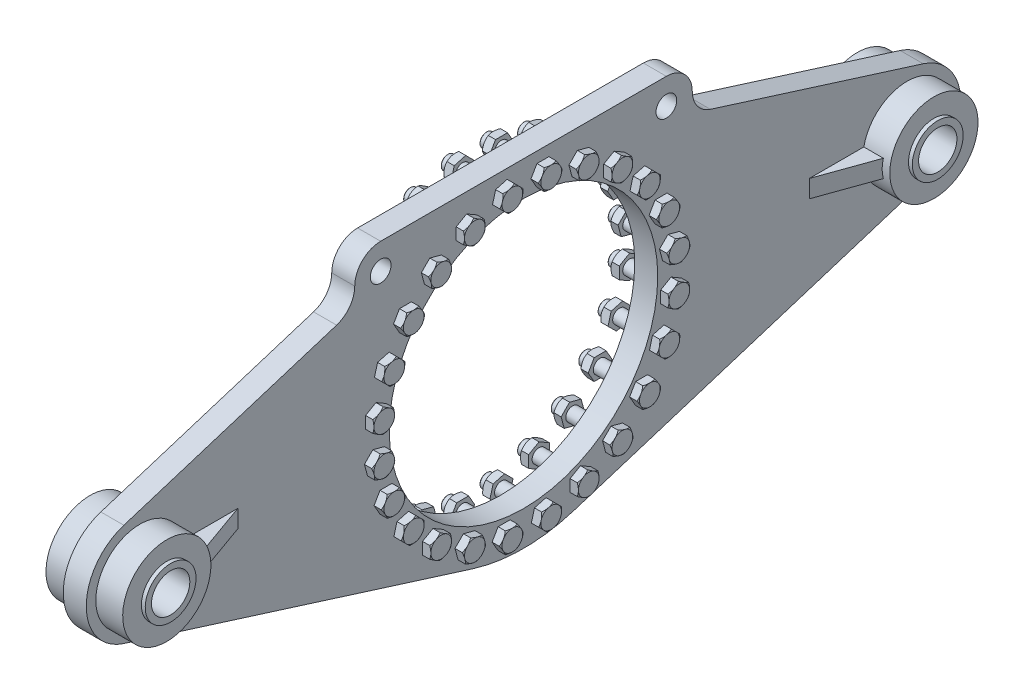
SolidWorks part; units mm, degrees
ref_plane "前视基准面" through (0, 0, 0) normal (0, 0, 1) x (1, 0, 0)
ref_plane "上视基准面" through (0, 0, 0) normal (0, 1, 0) x (1, 0, 0)
ref_plane "右视基准面" through (0, 0, 0) normal (1, 0, 0) x (0, 0, -1)
sketch "草图1" plane through (0, 0, 0) normal (1, 0, 0) x (0, 0, -1)
  line L0 (0, 0) -> (25.3221, 192.3403) construction
  line L1 (0, 220) -> (0, -220) construction
  line L2 (-500, 0) -> (500, 0) construction
  line L3 (0, 220) -> (-186.2221, 220)
  line L4 (-220, 186.2221) -> (-220, 0) construction
  line L5 (-243.6445, 154) -> (-521, 66.7757)
  line L6 (-186.2221, 186.2221) -> (-220, 186.2221) construction
  line L7 (-66, -209.8666) -> (-521, -66.7757)
  line L8 (-186.2221, 186.2221) -> (-186.2221, 220) construction
  circle A0 centre (0, 0) radius 194 construction
  circle A1 centre (0, 0) radius 175
  circle A2 centre (0, 0) radius 220
  circle A3 centre (25.3221, 192.3403) radius 9
  arc A4 (-521, 66.7757) -> (-521, -66.7757) centre (-500, 0) ccw
  circle A5 centre (-186.2221, 186.2221) radius 13.5
  circle A6 centre (-500, 0) radius 57.5
  circle A7 centre (-500, 0) radius 25
  arc A8 (-243.6445, 154) -> (-220, 186.2221) centre (-253.7779, 186.2221) ccw
  arc A9 (-186.2221, 220) -> (-220, 186.2221) centre (-186.2221, 186.2221) ccw
  point P10 (0, -24)
  point P12 (-372.5, 0)
  dimension "D1" = 7.5
  dimension "k" = 388
  dimension "d4" = 350
  dimension "D3" = 440
  dimension "D2" = 50
  dimension "s" = 18
  dimension "D5" = 70
  dimension "(d4)" = 115
  dimension "D7" = 27
  dimension "n" = 24
  dimension "n2" = 500
  dimension "P" = 1140
sketch "草图2" plane through (0, 0, 0) normal (0, 0, 1) x (1, 0, 0)
  line L0 (0, 220) -> (0, -220) construction
  line L1 (-15, 220) -> (15, 220)
  line L2 (-15, 220) -> (-15, -220)
  line L3 (-15, -220) -> (15, -220)
  line L4 (15, 220) -> (15, -220)
  line L7 (0, 0) -> (150, 0) construction
  point P9 (50, 0)
  point P12 (55, 0)
  point P13 (-50, 0)
  point P14 (-55, 0)
  point P15 (-39, 220)
  point P16 (-58.8, 220)
  dimension "D1" = 19.8
  dimension "G10" = 30
  dimension "G2" = 165
  dimension "l5" = 100
  dimension "l6" = 110
  dimension "(C)" = 24
ref_plane "基准面1" through (0, 0, 500) normal (0, 0, 1) x (1, 0, 0)
sketch "草图3" plane through (0, 0, 0) normal (1, 0, 0) x (0, 0, -1)
  line L0 (0, 220) -> (-186.2221, 220) construction
  line L1 (-243.6445, 154) -> (-521, 66.7757) construction
  line L2 (-66, -209.8666) -> (-521, -66.7757) construction
  line L3 (0, 220) -> (0, -220) construction
  line L4 (0, 220) -> (-186.2221, 220)
  line L5 (-243.6445, 154) -> (-521, 66.7757)
  line L6 (-66, -209.8666) -> (-521, -66.7757)
  line L7 (0, 220) -> (0, 175)
  line L8 (0, -175) -> (0, -220)
  arc A0 (-186.2221, 220) -> (-220, 186.2221) centre (-186.2221, 186.2221) ccw construction
  arc A1 (-243.6445, 154) -> (-220, 186.2221) centre (-253.7779, 186.2221) ccw construction
  circle A2 centre (-500, 0) radius 70 construction
  circle A3 centre (0, 0) radius 220 construction
  arc A4 (-186.2221, 220) -> (-220, 186.2221) centre (-186.2221, 186.2221) ccw
  arc A5 (-243.6445, 154) -> (-220, 186.2221) centre (-253.7779, 186.2221) ccw
  arc A6 (-521, 66.7757) -> (-521, -66.7757) centre (-500, 0) ccw
  arc A7 (-66, -209.8666) -> (0, -220) centre (0, 0) ccw
  circle A8 centre (0, 0) radius 175 construction
  circle A9 centre (-500, 0) radius 25 construction
  circle A10 centre (-500, 0) radius 25
  circle A11 centre (-186.2221, 186.2221) radius 13.5 construction
  circle A12 centre (-186.2221, 186.2221) radius 13.5
  arc A13 (0, 175) -> (0, -175) centre (0, 0) ccw
extrude "凸台-拉伸1" add sketch "草图3" against normal up to vertex (15 mm away) from vertex up to point (-15, 220, 0) starting at point (15, 220, 0)
sketch "草图4" plane through (0, 0, 500) normal (0, 0, 1) x (1, 0, 0)
  line L0 (-55, 0) -> (55, 0) construction
  line L1 (-55, 25) -> (-55, 33.125)
  line L2 (-55, 33.125) -> (-50, 33.125)
  line L3 (-50, 33.125) -> (-50, 57.5)
  line L4 (-50, 57.5) -> (50, 57.5)
  line L6 (-55, 25) -> (55, 25)
  line L8 (0, 0) -> (0, 25) construction
  line L17 (0, 25) -> (0, 33.125) construction
  line L18 (0, -57.5) -> (0, 57.5) construction
  line L19 (0, 33.125) -> (0, 41.25) construction
  line L20 (0, 41.25) -> (0, 49.375) construction
  line L21 (0, 49.375) -> (0, 57.5) construction
  line L22 (55, 25) -> (55, 33.125)
  line L23 (50, 33.125) -> (50, 57.5)
  line L24 (55, 33.125) -> (50, 33.125)
revolve "旋转1" add sketch "草图4" angle 360 about L0
sketch "草图10" plane through (0, 0, 0) normal (0, 1, 0) x (1, 0, 0)
  line L0 (15, -372.5) -> (40, -442.5)
  line L1 (15, -243.6445) -> (15, -521) construction
  line L8 (50, -442.5) -> (15, -442.5) construction
  line L9 (0, 0) -> (0, -500) construction
  dimension "D1" = 40
rib "筋16" sketch "草图10" sketch "草图10" thickness 23 extrusion direction parallel to sketch draft on no parameters "D1"=23
mirror "镜向1" about plane through (0, 0, 0) normal (1, 0, 0) of "筋16"
mirror "镜向2" about plane through (0, 0, 0) normal (0, 0, 1) of "镜向1", "旋转1", "筋16", "凸台-拉伸1"
sketch "草图11" plane through (0, 0, 0) normal (1, 0, 0) x (0, 0, -1)
  circle A0 centre (25.3221, 192.3403) radius 9 construction
  circle A1 centre (25.3221, 192.3403) radius 9
extrude "切除-拉伸1" cut sketch "草图11" against normal up to vertex (15 mm away) from vertex up to point (-15, 220, 0) starting at point (15, 220, 0)
pattern_circular "阵列(圆周)1" count 24 over 360 about axis through (-15, 0, 0) along (1, 0, 0) of "切除-拉伸1"
sketch "草图13" plane through (15, 203.4431, 56.7615) normal (1, 0, 0) x (0, 0, -1)
  line L1 (66.4951, -11.1028) -> (74.2894, -24.6028)
  line L2 (74.2894, -24.6028) -> (89.8778, -24.6028)
  line L3 (89.8778, -24.6028) -> (97.6721, -11.1028)
  line L4 (97.6721, -11.1028) -> (89.8778, 2.3972)
  line L5 (89.8778, 2.3972) -> (74.2894, 2.3972)
  line L6 (74.2894, 2.3972) -> (66.4951, -11.1028)
  circle A0 centre (82.0836, -11.1028) radius 13.5 construction
  dimension "D1" = 27
extrude "拉伸-螺栓" add sketch "草图13" along normal blind 10.8
sketch "草图21" plane through (25.8, 192.3403, -25.3221) normal (1, 0, 0) x (0, 0, -1)
  line L0 (13.5, 0) -> (17.6769, 0) construction
  circle A0 centre (0, 0) radius 13.5 construction
  circle A1 centre (0, 0) radius 13.5
  circle A2 centre (0, 0) radius 17.6769
extrude "切除-螺栓" cut sketch "草图21" against normal up to vertex (10.8 mm away) draft 55 up to point (15, 192.3403, -40.9105)
sketch "草图22" plane through (0, 0, 0) normal (1, 0, 0) x (0, 0, -1)
  circle A0 centre (25.3221, 192.3403) radius 9 construction
  circle A1 centre (25.3221, 192.3403) radius 9
extrude "凸台-拉伸4" add sketch "草图22" against normal up to vertex (58.8 mm away) from vertex up to point (-58.8, 220, 0) starting at point (15, 220, 0)
chamfer "倒角1" distance 0.9 angle 45 1 edges at (-58.8, 192.3403, -34.3221)
extrude "凸台-拉伸5" add sketch "草图13<2>" against normal blind 10.8 from vertex starting at point (-39, 220, 0)
sketch "草图13<2>" plane through (15, 203.4431, 56.7615) normal (1, 0, 0) x (0, 0, -1) same geometry as "草图13"
sketch "草图23" plane through (-49.8, 0, 0) normal (-1, 0, 0) x (0, 0, 1)
  line L0 (-38.8221, 192.3403) -> (-42.999, 192.3403) construction
  circle A0 centre (-25.3221, 192.3403) radius 17.6769
  circle A1 centre (-25.3221, 192.3403) radius 13.5
  circle A2 centre (-25.3221, 192.3403) radius 13.5 construction
extrude "切除-拉伸3" cut sketch "草图23" against normal up to vertex (10.8 mm away) draft 55 up to point (-39, 205.8403, -33.1163)
pattern_circular "阵列(圆周)2" count 24 over 360 about axis through (-15, 0, 0) along (1, 0, 0) of "切除-拉伸3", "凸台-拉伸5", "倒角1", "凸台-拉伸4", "切除-螺栓", "拉伸-螺栓"
equation "\"D1@草图1\" = 180/\"n@草图1\""
equation "\"D5@草图1\" = (  \"P@草图1\" - \"n2@草图1\" * 2 )  / 2"
equation "\"D7@草图1\" = \"s@草图1\" * 1.5"
equation "\"D1@草图10\" = \"l5@草图2\" * 0.4"
equation "\"D1@筋16\" = \"(d4)@草图1\" * 0.2"
equation "\"D1@阵列(圆周)1\" = \"n@草图1\""
equation "\"D1@草图2\" = \"s@草图1\" * 1.1"
equation "\"D1@草图13\" =1.5*\"s@草图1\""
equation "\"D1@拉伸-螺栓\" = \"D1@草图13\"*0.4"
equation "\"D1@倒角1\" = \"s@草图1\" * 0.05"
equation "\"D1@凸台-拉伸5\" = \"D1@拉伸-螺栓\""
equation "\"D1@阵列(圆周)2\" = \"n@草图1\""
